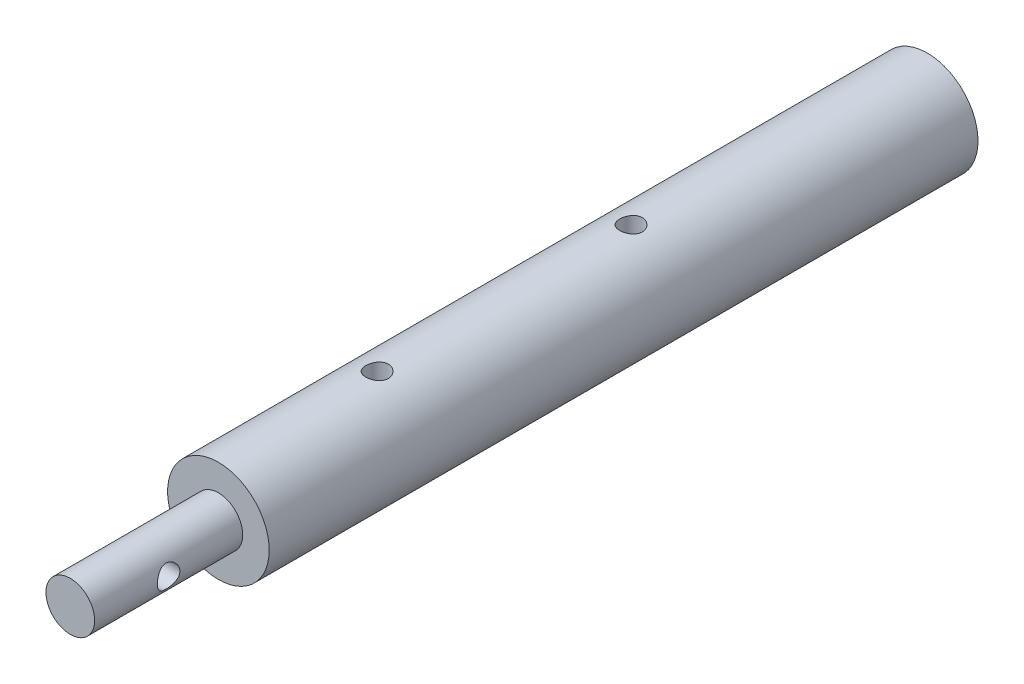
SolidWorks part; units mm, degrees
ref_plane "Front Plane" through (0, 0, 0) normal (0, 0, 1) x (1, 0, 0)
ref_plane "Top Plane" through (0, 0, 0) normal (0, 1, 0) x (1, 0, 0)
ref_plane "Right Plane" through (0, 0, 0) normal (1, 0, 0) x (0, 0, -1)
sketch "Sketch1" plane through (0, 0, 0) normal (0, 0, 1) x (1, 0, 0)
  circle A0 centre (0, 0) radius 6.096
  dimension "D1" = 12.192
extrude "Boss-Extrude1" add sketch "Sketch1" along normal blind 85.09
sketch "Sketch2" plane through (0, 0, 85.09) normal (0, 0, 1) x (1, 0, 0)
  circle A0 centre (0, 0) radius 2.921
  dimension "D1" = 5.842
extrude "Boss-Extrude2" add sketch "Sketch2" along normal blind 17.78
ref_plane "Plane1" through (0, 6.096, 0) normal (0, 1, 0) x (1, 0, 0)
sketch "Sketch4" plane through (0, 6.096, 0) normal (0, 1, 0) x (1, 0, 0)
  line L1 (-2.921, -102.87) -> (2.921, -102.87) construction
  circle A0 centre (0, -35.56) radius 1.8415
  circle A1 centre (0, -66.04) radius 1.8415
  dimension "D1" = 3.683
  dimension "D2" = 67.31
  dimension "D3" = 36.83
hole_wizard "#6-32 Tapped Hole1" positions "Sketch5" profile "Sketch6" tap size "#6-32" standard "ANSI Inch" end condition through all
sketch "Sketch5" plane through (0, 6.096, 0) normal (0, 1, 0) x (1, 0, 0)
  point P0 (0, -35.56)
  point P3 (0, -66.04)
sketch "Sketch6" plane through (0, 6.096, 35.56) normal (1, 0, 0) x (0, 0, 1)
  line L0 (0, 0) -> (0, 12.192)
  line L1 (0, 12.192) -> (1.3525, 12.192)
  line L2 (1.3525, 12.192) -> (1.3525, 0)
  line L5 (1.3525, 0) -> (0, 0)
  line L11 (0, -6.35) -> (0, 107.95) construction
  dimension "Thru Tap Drill Dia." = 2.7051
  dimension "Thru Tap Drill Depth" = 12.192
cosmetic thread "Hole Thread1" parameters "D2"=3.5052
cosmetic thread "Hole Thread2" parameters "D2"=3.5052
ref_plane "Plane2" through (2.921, 0, 0) normal (1, 0, 0) x (0, 0, -1)
sketch "Sketch7" plane through (2.921, 0, 0) normal (1, 0, 0) x (0, 0, -1)
  line L1 (-102.87, 2.921) -> (-102.87, -2.921) construction
  circle A0 centre (-93.98, 0) radius 1.8415
  dimension "D1" = 3.683
  dimension "D2" = 8.89
hole_wizard "#6-32 Tapped Hole2" positions "Sketch8" profile "Sketch9" tap size "#6-32" standard "ANSI Inch" end condition through all
sketch "Sketch8" plane through (2.921, 0, 0) normal (1, 0, 0) x (0, 0, -1)
  point P0 (-93.98, 0)
sketch "Sketch9" plane through (2.921, 0, 93.98) normal (0, 1, 0) x (0, 0, -1)
  line L0 (0, 0) -> (0, 9.017)
  line L1 (0, 9.017) -> (1.3525, 9.017)
  line L2 (1.3525, 9.017) -> (1.3525, 0)
  line L5 (1.3525, 0) -> (0, 0)
  line L11 (0, -6.35) -> (0, 107.95) construction
  dimension "Thru Tap Drill Dia." = 2.7051
  dimension "Thru Tap Drill Depth" = 9.017
cosmetic thread "Hole Thread3" parameters "D2"=3.5052
